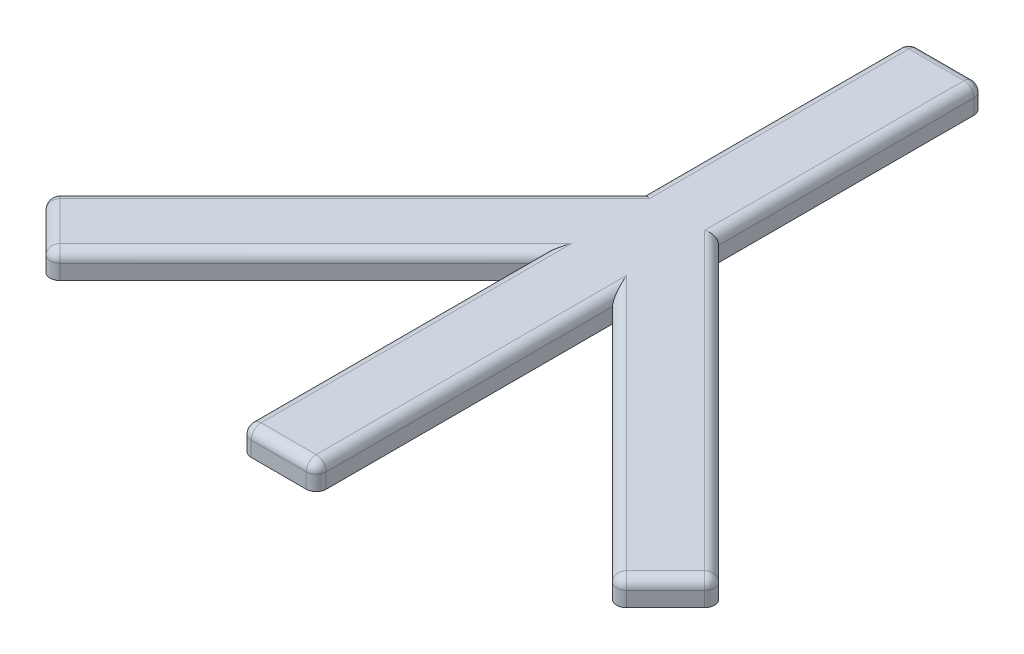
SolidWorks part; units mm, degrees
ref_plane "Front Plane" through (0, 0, 0) normal (0, 0, 1) x (1, 0, 0)
ref_plane "Top Plane" through (0, 0, 0) normal (0, 1, 0) x (1, 0, 0)
ref_plane "Right Plane" through (0, 0, 0) normal (1, 0, 0) x (0, 0, -1)
sketch "Sketch1" plane through (0, 0, 0) normal (0, 1, 0) x (1, 0, 0)
  line L3 (-56.5917, -56.5917) -> (-67.1983, -45.9851)
  line L4 (-7.5, -66.694) -> (7.5, -66.694)
  line L5 (-7.5, -66.694) -> (-7.5, 66.694)
  line L6 (-7.5, 66.694) -> (7.5, 66.694)
  line L7 (7.5, -66.694) -> (7.5, 66.694)
  line L10 (-56.5917, -56.5917) -> (6.4844, 6.4844)
  line L11 (-67.1983, -45.9851) -> (-4.1222, 17.091)
  line L12 (6.4844, 6.4844) -> (-4.1222, 17.091)
  line L17 (56.5917, -56.5917) -> (67.1983, -45.9851)
  line L18 (56.5917, -56.5917) -> (-7.0272, 7.0272)
  line L19 (67.1983, -45.9851) -> (3.5794, 17.6338)
  line L20 (-7.0272, 7.0272) -> (3.5794, 17.6338)
  point P4 (0, 0)
  dimension "D1" = 15
  dimension "D2" = 15
  dimension "D3" = 15
extrude "Boss-Extrude4" add sketch "Sketch1" along normal blind 5 contours L17 L19 L7 L18 | L11 L3 L10 L5 | L5 L4 L7 L6 region at (-34.7837, 0, 23.8324) region at (34.7837, 0, 23.8324)
fillet "Fillet2" radius 2 12 edges at (0, 5, -66.694) (61.895, 5, 51.2884) (0, 5, 66.694) (-61.895, 5, 51.2884) (-37.3492, 5, 16.136) (-7.5, 5, -40.2036) (37.3492, 5, 16.136) (7.5, 5, -40.2036) (7.5, 5, 37.097) (32.0459, 5, 32.0459) (-7.5, 5, 37.097) (-32.0459, 5, 32.0459)
fillet "Fillet3" radius 2 16 edges at (6.9142, 4.4142, -66.1082) (-6.9142, 4.4142, -66.1082) (-66.3699, 4.4142, 45.9851) (-56.5917, 4.4142, 55.7633) (66.3699, 4.4142, 45.9851) (56.5917, 4.4142, 55.7633) (-6.9142, 4.4142, 66.1082) (6.9142, 4.4142, 66.1082) (7.5, 1.5, -66.694) (-7.5, 1.5, -66.694) (-67.1983, 1.5, 45.9851) (-56.5917, 1.5, 56.5917) (67.1983, 1.5, 45.9851) (56.5917, 1.5, 56.5917) (-7.5, 1.5, 66.694) (7.5, 1.5, 66.694)
